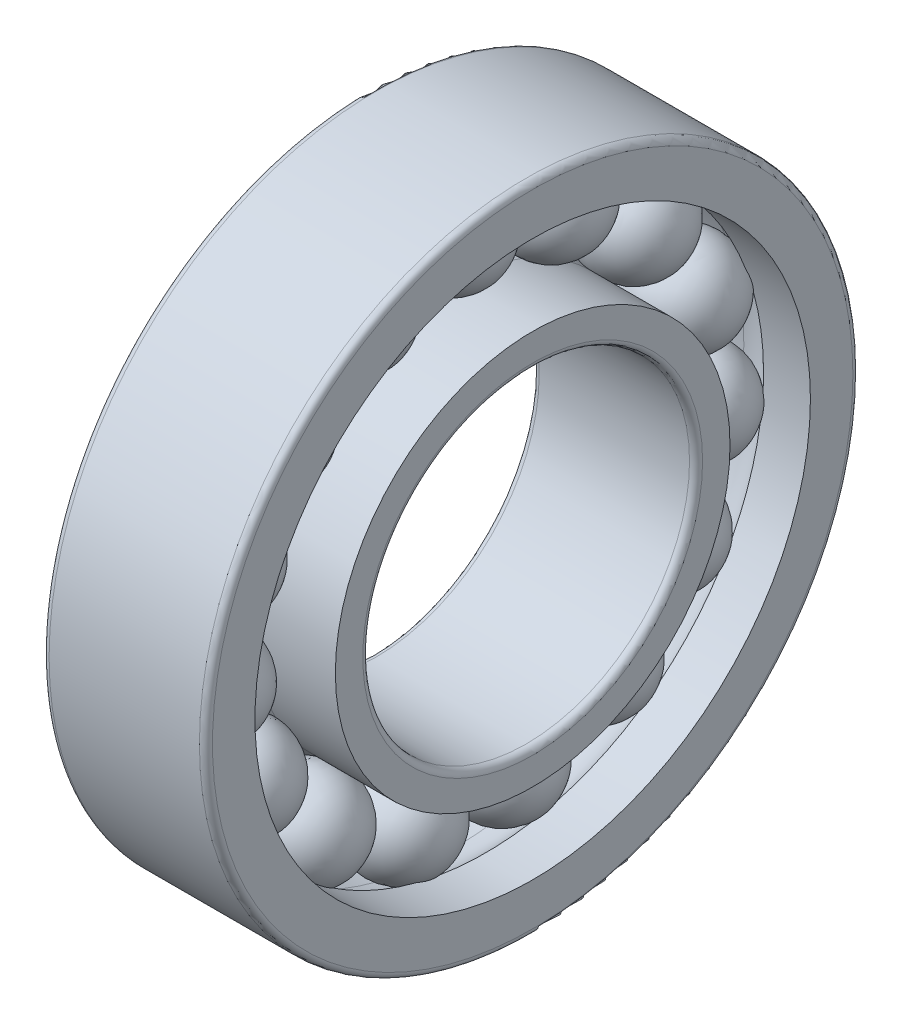
SolidWorks part; units mm, degrees
ref_plane "Plane1" through (0, 0, 0) normal (0, 0, 1) x (1, 0, 0)
ref_plane "Plane2" through (0, 0, 0) normal (0, 1, 0) x (1, 0, 0)
ref_plane "Plane3" through (0, 0, 0) normal (1, 0, 0) x (0, 0, -1)
sketch "Clipboard" plane through (0, 0, 0) normal (0, 0, 1) x (1, 0, 0)
  line L0 (-10, 0) -> (10, 0) construction
  line L1 (0, 0) -> (21.5988, -5.7874)
  line L2 (0, 0) -> (4.7618, -0.0831)
  line L3 (0, 0) -> (22.3573, 0.3902)
  line L4 (0, 0) -> (-22.3573, -0.3902)
  dimension "BallCLRad" = 4.7625
sketch "CagSpiSke" plane through (0, 0, 0) normal (0, 0, 1) x (1, 0, 0)
  line L0 (0.0952, 4.6038) -> (0.0953, 4.9213)
  line L1 (0.0953, 4.9213) -> (-0.0953, 4.9213)
  line L2 (-0.0953, 4.9213) -> (-0.0952, 4.6038)
  line L3 (-0.0952, 4.6038) -> (0.0952, 4.6038)
  line L4 (-20.6375, 0) -> (20.6375, 0) construction
  line L5 (0, 0) -> (0, 23.7692) construction
  dimension "OD" = 9.8425
  dimension "ID" = 9.2075
revolve "CageSpine" add sketch "CagSpiSke" angle 0.001 about L4 reverse direction yes
ref_axis "Axis1" through (-50, 0, 0) along (1, 0, 0)
sketch "CagBalSke" plane through (0, 0, 0) normal (0, 0, 1) x (1, 0, 0)
  line L0 (-1.0478, 4.7625) -> (1.0478, 4.7625)
  line L1 (-1.905, 4.7625) -> (1.905, 4.7625) construction
  line L2 (-10, 0) -> (10, 0) construction
  line L3 (0, 0) -> (0, 24) construction
  arc A0 (1.0478, 4.7625) -> (-1.0478, 4.7625) centre (0, 4.7625) cw
  dimension "BallCLRad" = 4.7625
revolve "CageBall" [suppressed] add sketch "CagBalSke" angle 360 about L1 reverse direction yes
pattern_circular "CageBalls" [suppressed] count 15 every 24 about axis through (-50, 0, 0) along (1, 0, 0)
sketch "CagTrmODSke" plane through (0, 0, 0) normal (0, 0, 1) x (1, 0, 0)
  line L0 (1.0488, 4.9212) -> (1.0488, 5.8113)
  line L1 (1.0488, 5.8113) -> (-1.0488, 5.8113)
  line L2 (-1.0488, 5.8113) -> (-1.0488, 4.9212)
  line L3 (-1.0488, 4.9212) -> (1.0488, 4.9212)
  line L4 (-20.6375, 0) -> (20.6375, 0) construction
  line L5 (0, 0) -> (0, 25) construction
  dimension "Width" = 2.0975
  dimension "ID" = 9.8425
  dimension "OD" = 11.6225
revolve "CageTrimOD" [suppressed] cut sketch "CagTrmODSke" angle 360 about L4 reverse direction yes
sketch "CagTrmIDSke" plane through (0, 0, 0) normal (0, 0, 1) x (1, 0, 0)
  line L0 (1.0487, 3.7158) -> (1.0488, 4.6037)
  line L1 (1.0488, 4.6037) -> (-1.0488, 4.6037)
  line L2 (-1.0488, 4.6037) -> (-1.0487, 3.7158)
  line L3 (-1.0487, 3.7158) -> (1.0487, 3.7158)
  line L4 (-20.6375, 0) -> (20.6375, 0) construction
  line L5 (0, 0) -> (0, 25) construction
  dimension "Width" = 2.0975
  dimension "ID" = 7.4315
  dimension "OD" = 9.2075
revolve "CageTrimID" [suppressed] cut sketch "CagTrmIDSke" angle 360 about L4 reverse direction yes
sketch "BalSimSke" plane through (0, 0, 0) normal (0, 0, 1) x (1, 0, 0)
  line L0 (-10, 0) -> (10, 0) construction
  line L1 (-10, 4.7625) -> (10, 4.7625) construction
  line L2 (0, 0) -> (0, 23) construction
  circle A0 centre (0, 4.7625) radius 0.9525
  dimension "BallCLRad" = 4.7625
  dimension "Ball_diameter" = 1.905
revolve "BallsSimplified" [suppressed] add sketch "BalSimSke" angle 360 about L0
sketch "BalDetSke" plane through (0, 0, 0) normal (0, 0, 1) x (1, 0, 0)
  line L0 (-0.9525, 4.7625) -> (0.9525, 4.7625)
  line L1 (-1.905, 4.7625) -> (1.905, 4.7625) construction
  line L2 (0, 0) -> (0, 25) construction
  arc A0 (0.9525, 4.7625) -> (-0.9525, 4.7625) centre (0, 4.7625) cw
  dimension "BallCLRad" = 4.7625
  dimension "Ball_diameter" = 1.905
revolve "BallDetailed" add sketch "BalDetSke" angle 360 about L1 reverse direction yes
sketch "InnRacSke" plane through (0, 0, 0) normal (0, 0, 1) x (1, 0, 0)
  line L0 (-0.676, 4.1275) -> (-1.5875, 4.1275)
  line L1 (-1.5875, 4.1275) -> (-1.5875, 3.302)
  line L2 (-1.4605, 3.175) -> (1.4605, 3.175)
  line L3 (1.5875, 3.302) -> (1.5875, 3.835)
  line L4 (0, 3.835) -> (1.5875, 3.835)
  line L5 (-20.6375, 0) -> (20.6375, 0) construction
  line L6 (0, 0) -> (0, 30) construction
  arc A0 (-1.5875, 3.302) -> (-1.4605, 3.175) centre (-1.4605, 3.302) ccw
  arc A1 (1.4605, 3.175) -> (1.5875, 3.302) centre (1.4605, 3.302) ccw
  arc A2 (0, 3.835) -> (-0.676, 4.1275) centre (0, 4.7625) cw
  dimension "BallCLRad" = 4.7625
  dimension "Fillet_radius" = 0.127
  dimension "Ball_diameter" = 1.855
  dimension "ID" = 6.35
  dimension "OD" = 8.255
  dimension "Width" = 3.175
revolve "InnerRace" add sketch "InnRacSke" angle 360 about L5 reverse direction yes
sketch "OutRacSke" plane through (0, 0, 0) normal (0, 0, 1) x (1, 0, 0)
  line L0 (0, 5.69) -> (-1.5875, 5.69)
  line L1 (-1.5875, 5.69) -> (-1.5875, 6.223)
  line L2 (-1.4605, 6.35) -> (1.4605, 6.35)
  line L3 (1.5875, 6.223) -> (1.5875, 5.3975)
  line L4 (1.5875, 5.3975) -> (0.676, 5.3975)
  line L5 (-20.6375, 0) -> (20.6375, 0) construction
  line L6 (0, 0) -> (0, 30) construction
  arc A0 (-1.5875, 6.223) -> (-1.4605, 6.35) centre (-1.4605, 6.223) cw
  arc A1 (1.4605, 6.35) -> (1.5875, 6.223) centre (1.4605, 6.223) cw
  arc A2 (0.676, 5.3975) -> (0, 5.69) centre (0, 4.7625) ccw
  dimension "BallCLRad" = 4.7625
  dimension "Fillet_radius" = 0.127
  dimension "Ball_diameter" = 1.855
  dimension "Width" = 3.175
revolve "OuterRace" add sketch "OutRacSke" angle 360 about L5 reverse direction yes
pattern_circular "BallsDetailed" count 15 every 24 about axis through (-50, 0, 0) along (1, 0, 0) of "BallDetailed"
equation "\"BallCLRad@Clipboard\" = ( \"OD@OutRacSke\" + \"ID@InnRacSke\" ) / 4"
equation "\"BallCLRad@BalSimSke\" = \"BallCLRad@Clipboard\""
equation "\"BallCLRad@BalDetSke\" = \"BallCLRad@Clipboard\""
equation "\"BallCLRad@InnRacSke\" = \"BallCLRad@Clipboard\""
equation "\"BallCLRad@OutRacSke\" = \"BallCLRad@Clipboard\""
equation "\"Ball_diameter@InnRacSke\" = \"Ball_diameter@BalDetSke\" - 0.05"
equation "\"Ball_diameter@OutRacSke\" = \"Ball_diameter@BalDetSke\" - 0.05"
equation "\"Ball_diameter@BalSimSke\" = \"Ball_diameter@BalDetSke\""
equation "\"Width@OutRacSke\" = \"Width@InnRacSke\""
equation "\"Fillet_radius@OutRacSke\" = \"Fillet_radius@InnRacSke\""
equation "\"Max_count@Clipboard\" = int( 3.14159265 / atn(( \"Ball_diameter@BalDetSke\" / 2) / sqr( \"BallCLRad@Clipboard\"  *  \"BallCLRad@Clipboard\" - ( \"Ball_diameter@BalDetSke\" / 2) *  ( \"Ball_diameter@BalDetSke\" / 2))))"
equation "\"Max_count@Clipboard\" = ((sgn( \"Max_count@Clipboard\" - \"Count@Clipboard\" )-1)*( \"Max_count@Clipboard\" - \"Count@Clipboard\" ))/-2+ \"Count@Clipboard\""
equation "\"Count@BallsDetailed\" = int( \"Show_count@Clipboard\" ) "
equation "\"Count@BallsDetailed\" = ((sgn( \"Count@BallsDetailed\" - \"Max_count@Clipboard\" )-1)*( \"Count@BallsDetailed\" - \"Max_count@Clipboard\" ))/-2+ \"Max_count@Clipboard\""
equation "\"Count@BallsDetailed\" = ((sgn( \"Count@BallsDetailed\" - \"Min_count@Clipboard\" )+1)*( \"Count@BallsDetailed\" - \"Min_count@Clipboard\"))/2 +\"Min_count@Clipboard\""
equation "\"Angle@BallsDetailed\" = 360.0 / \"Max_count@Clipboard\""
equation "\"BallCLRad@CagBalSke\" = \"BallCLRad@Clipboard\""
equation "\"Count@CageBalls\" = \"Count@BallsDetailed\""
equation "\"Angle@CageBalls\" = \"Angle@BallsDetailed\""
equation "\"Angle@CageSpine\" =  \"Angle@CageBalls\" * ( \"Count@CageBalls\" -1 + int( \"Count@CageBalls\" / \"Max_count@Clipboard\" ) )  + 0.001 -  int( \"Count@CageBalls\" / \"Max_count@Clipboard\" ) * 0.001"
equation "\"Angle@CageSpine\" =  \"Angle@CageSpine\" * int( \"Min_count@Clipboard\" / 2) + int(1 / \"Min_count@Clipboard\")  * 0.001"
equation "\"CageWallOD@CagBalSke\" =  \"Ball_diameter@BalDetSke\" * 1.1"
equation "\"Thickness@CagSpiSke\" =  \"Ball_diameter@BalDetSke\" * 0.1"
equation "\"OD@CagTrmODSke\" = \"BallCLRad@Clipboard\" * 2 + \"CageWallOD@CagBalSke\" + 0.002"
equation "\"ID@CagTrmODSke\" = \"BallCLRad@Clipboard\" * 2 + \"Ball_diameter@BalDetSke\" / 6"
equation "\"OD@CagTrmIDSke\" = \"BallCLRad@Clipboard\" * 2 - \"Ball_diameter@BalDetSke\" / 6"
equation "\"ID@CagTrmIDSke\" = \"BallCLRad@Clipboard\" * 2 - \"CageWallOD@CagBalSke\" + 0.002"
equation "\"OD@CagSpiSke\" = \"ID@CagTrmODSke\""
equation "\"ID@CagSpiSke\" = \"OD@CagTrmIDSke\""
equation "\"Width@CagTrmODSke\" = \"CageWallOD@CagBalSke\" + 0.002"
equation "\"Width@CagTrmIDSke\" = \"CageWallOD@CagBalSke\" + 0.002"
